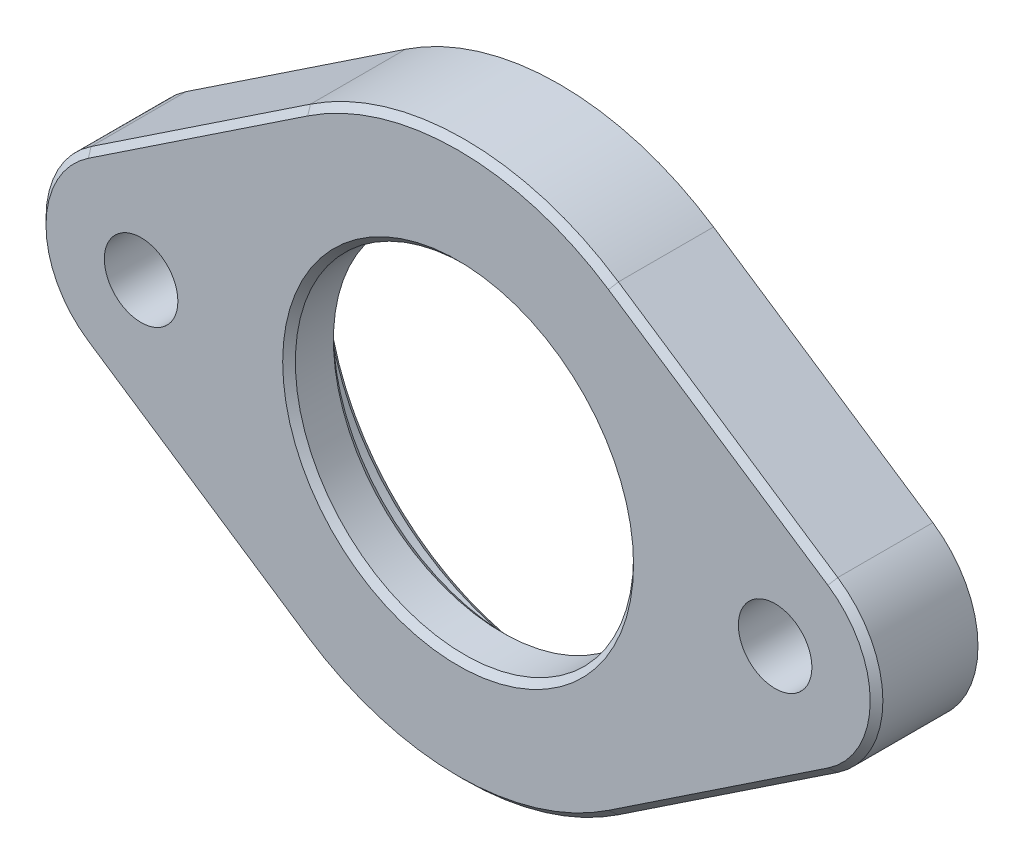
SolidWorks part; units mm, degrees
material "ABS"
ref_plane "Front Plane" through (0, 0, 0) normal (0, 0, 1) x (1, 0, 0)
ref_plane "Top Plane" through (0, 0, 0) normal (0, 1, 0) x (1, 0, 0)
ref_plane "Right Plane" through (0, 0, 0) normal (1, 0, 0) x (0, 0, -1)
sketch "Sketch1" plane through (0, 0, 0) normal (0, 0, 1) x (1, 0, 0)
  line L0 (-12.5, 0) -> (12.5, 0)
  line L1 (-6.0703, -9.0984) -> (-14.72, -3.3274)
  line L2 (-6.0703, 9.0984) -> (-14.72, 3.3274)
  line L3 (6.0703, 9.0984) -> (14.72, 3.3274)
  line L4 (6.0703, -9.0984) -> (14.72, -3.3274)
  circle A0 centre (0, 0) radius 6.6675
  circle A1 centre (0, 0) radius 8.9375
  circle A2 centre (0, 0) radius 10.9375
  circle A3 centre (-12.5, 0) radius 4
  circle A4 centre (12.5, 0) radius 4
  point P7 (0, 0)
  dimension "D1" = 13.335
  dimension "D2" = 17.875
  dimension "D4" = 8
  dimension "D3" = 2
  dimension "D5" = 25
extrude "Boss-Extrude1" add sketch "Sketch1" along normal blind 4 contours A3 L0 A2 L2 | A3 L1 A2 L0 | A3 | A4 L3 A2 L0 | A4 | A4 L0 A2 L4 | A2 region at (13.2988, 0, 0) region at (10.617, 5.2562, 0) region at (10.617, -5.2562, 0) region at (-10.617, 5.2562, 0) region at (-13.2988, 0, 0) region at (-10.617, -5.2562, 0)
extrude "Cut-Extrude1" cut sketch "Sketch1<4>" against normal through all both and the other way through all contours L0 A0 | L0 A0 region at (0, -2.8298, 0) region at (0, 2.8298, 0)
sketch "Sketch1<4>" plane through (0, 0, 0) normal (0, 0, 1) x (1, 0, 0) same geometry as "Sketch1"
extrude "Cut-Extrude2" cut sketch "Sketch1<6>" along normal blind 2 and the other way through all contours A1
sketch "Sketch1<6>" plane through (0, 0, 0) normal (0, 0, 1) x (1, 0, 0) same geometry as "Sketch1"
sketch "Sketch2" plane through (0, 0, 4) normal (0, 0, 1) x (1, 0, 0)
  point P0 (-12.5, 0)
  point P3 (12.5, 0)
hole_wizard "M2.5 Clearance Hole1" positions "Sketch2" profile "Sketch3" hole size "M2.5" standard "ANSI Metric" end condition through all
sketch "Sketch3" plane through (-12.5, 0, 4) normal (1, 0, 0) x (0, -1, 0)
  line L0 (0, 0) -> (0, 4)
  line L1 (0, 4) -> (1.45, 4)
  line L2 (1.45, 4) -> (1.45, 0)
  line L5 (1.45, 0) -> (0, 0)
  line L11 (0, -6.35) -> (0, 107.95) construction
  dimension "Thru Hole Dia." = 2.9
  dimension "Thru Hole Depth" = 4
chamfer "Chamfer1" distance 0.25 angle 45 12 edges at (6.6675, 0, 4) (6.6675, 0, 2) (8.9375, 0, 0) (8.9375, 0, 2) (10.3952, -6.2129, 4) (16.5, 0, 4) (0, -10.9375, 4) (10.3952, 6.2129, 4) (-10.3952, -6.2129, 4) (0, 10.9375, 4) (-16.5, 0, 4) (-10.3952, 6.2129, 4)
equation "\"D2@Sketch1\"=15.875mm+2"
